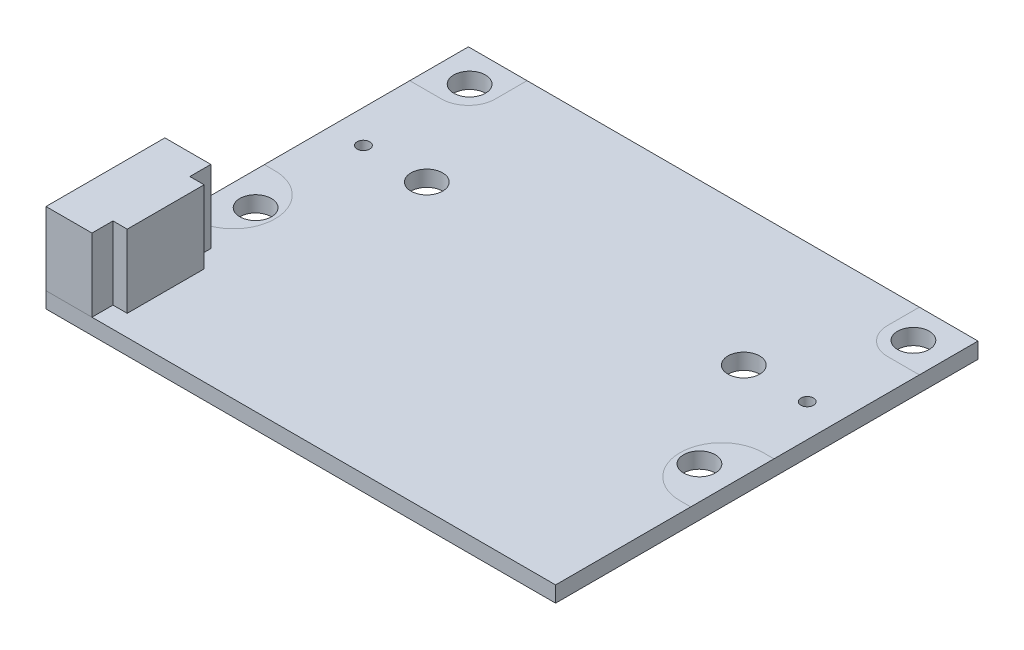
SolidWorks part; units mm, degrees
ref_plane "Front" through (0, 0, 0) normal (0, 0, 1) x (1, 0, 0)
ref_plane "Top" through (0, 0, 0) normal (0, 1, 0) x (1, 0, 0)
ref_plane "Right" through (0, 0, 0) normal (1, 0, 0) x (0, 0, -1)
sketch "Sketch1" plane through (0, 0, 0) normal (0, 1, 0) x (1, 0, 0)
  line L0 (0, 0) -> (0, 16268.1919) construction
  line L1 (0, 0) -> (16268.1919, 0) construction
  line L3 (-16.075, -17.95) -> (16.075, -17.95)
  line L4 (-16.075, -17.95) -> (-16.075, 8.7)
  line L5 (-16.075, 8.7) -> (16.075, 8.7)
  line L6 (16.075, -17.95) -> (16.075, 8.7)
  circle A0 centre (14, 6.7) radius 1
  circle A1 centre (14, -6.8) radius 1
  circle A2 centre (14, 0) radius 0.4
  circle A3 centre (10, 0) radius 1
  circle A4 centre (-14, 0) radius 0.4
  circle A5 centre (-14, -6.8) radius 1
  circle A6 centre (-14, 6.7) radius 1
  circle A7 centre (-10, 0) radius 1
  point P17 (0, 0)
  point P18 (0, 0)
  dimension "D4" = 0.8
  dimension "D5" = 2
  dimension "D6" = 13.5
  dimension "D7" = 28
  dimension "D8" = 2
  dimension "D9" = 2
  dimension "D10" = 20
  dimension "D1" = 26.65
  dimension "D2" = 32.15
  dimension "D3" = 8.7
extrude "Boss-Extrude1" add sketch "Sketch1" along normal blind 1
sketch "Sketch4" plane through (0, 1, 0) normal (0, 1, 0) x (1, 0, 0)
  line L0 (16.075, 5) -> (14.075, 5)
  line L1 (16.075, 8.7) -> (-16.075, 8.7) construction
  line L2 (16.075, -17.95) -> (16.075, 8.7) construction
  line L3 (16.075, 5) -> (16.075, 8.7)
  line L4 (16.075, 8.7) -> (12.375, 8.7)
  line L5 (16.075, -9.425) -> (16.075, -4.175)
  line L6 (0, -0.1285) -> (0, -50000.1285) construction
  line L7 (14, -6.8) -> (-49986, -6.8) construction
  line L8 (14, 6.7) -> (-49986, 6.7) construction
  line L9 (12.375, 8.7) -> (12.375, 6.7)
  line L10 (16.075, -4.175) -> (15.4, -4.175)
  line L11 (16.075, -9.425) -> (15.4, -9.425)
  line L12 (-16.075, -9.425) -> (-15.4, -9.425)
  line L13 (-16.075, -4.175) -> (-15.4, -4.175)
  line L14 (-12.375, 8.7) -> (-12.375, 6.7)
  line L15 (-16.075, -9.425) -> (-16.075, -4.175)
  line L16 (-16.075, 8.7) -> (-12.375, 8.7)
  line L17 (-16.075, 5) -> (-16.075, 8.7)
  line L18 (-16.075, 5) -> (-14.075, 5)
  arc A2 (12.375, 6.7) -> (14.075, 5) centre (14.075, 6.7) ccw
  arc A3 (15.4, -4.175) -> (15.4, -9.425) centre (15.4, -6.8) ccw
  arc A4 (-15.4, -4.175) -> (-15.4, -9.425) centre (-15.4, -6.8) cw
  arc A5 (-12.375, 6.7) -> (-14.075, 5) centre (-14.075, 6.7) cw
  dimension "D1" = 5.25
  dimension "D3" = 3.3
  dimension "D2" = 3.7
split line "Split Line1"
sketch "Sketch5" plane through (0, 1, 0) normal (0, 1, 0) x (1, 0, 0)
  line L0 (-16.075, -14.2) -> (49983.925, -14.2) construction
  line L1 (-16.075, -17.95) -> (-13.175, -17.95)
  line L2 (-16.075, -17.95) -> (-16.075, -10.45)
  line L3 (-16.075, -10.45) -> (-13.175, -10.45)
  line L4 (-13.175, -17.95) -> (-13.175, -16.625)
  line L5 (-13.175, -16.625) -> (-12.275, -16.625)
  line L7 (-13.175, -11.775) -> (-12.275, -11.775)
  line L8 (-12.275, -16.625) -> (-12.275, -11.775)
  line L9 (-13.175, -11.775) -> (-13.175, -10.45)
  point P11 (-16.075, -14.2)
  dimension "D1" = 7.5
  dimension "D2" = 3.8
  dimension "D3" = 2.9
  dimension "D4" = 4.85
extrude "Boss-Extrude3" add sketch "Sketch5" along normal blind 4.6 separate body
ref_point "Point1"
